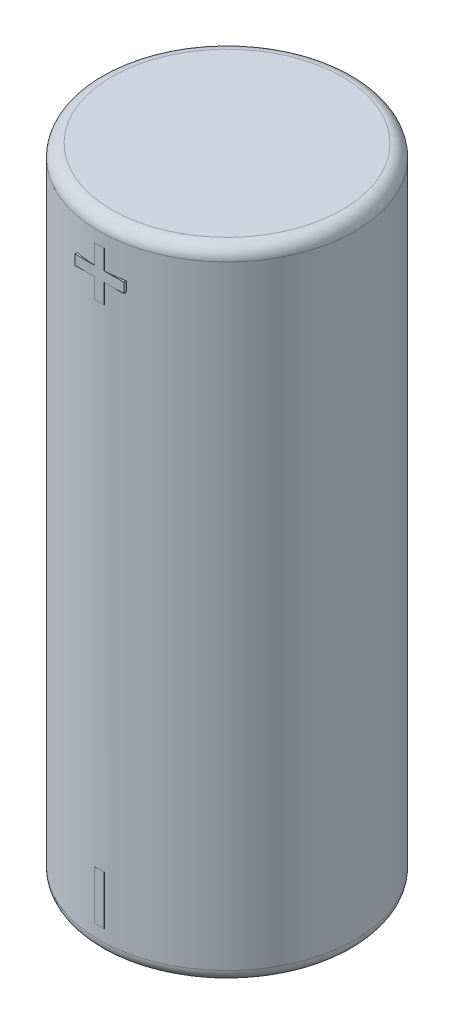
SolidWorks part; units mm, degrees
ref_plane "Front Plane" through (0, 0, 0) normal (0, 0, 1) x (1, 0, 0)
ref_plane "Top Plane" through (0, 0, 0) normal (0, 1, 0) x (1, 0, 0)
ref_plane "Right Plane" through (0, 0, 0) normal (1, 0, 0) x (0, 0, -1)
sketch "Sketch1" plane through (0, 0, 0) normal (0, 1, 0) x (1, 0, 0)
  circle A0 centre (0, 0) radius 13
  dimension "D1" = 26
extrude "Boss-Extrude1" add sketch "Sketch1" along normal blind 65
fillet "Fillet1" radius 1.27 1 edges at (0, 65, 13)
fillet "Fillet2" radius 1.27 1 edges at (0, 0, 13)
ref_plane "Plane1" through (0, 0, 13) normal (0, 0, 1) x (1, 0, 0)
sketch "Sketch2" plane through (0, 0, 13) normal (0, 0, 1) x (1, 0, 0)
  line L0 (11.73, 65) -> (-11.73, 65) construction
  line L1 (11.73, 65) -> (-11.73, 65)
  line L2 (0, 65) -> (0, 0) construction
  line L4 (-0.5, 62.5) -> (0.5, 62.5)
  line L5 (-0.5, 62.5) -> (-0.5, 57.5)
  line L6 (-0.5, 57.5) -> (0.5, 57.5)
  line L7 (0.5, 62.5) -> (0.5, 57.5)
  line L8 (-2.5, 60.5) -> (2.5, 60.5)
  line L9 (-2.5, 60.5) -> (-2.5, 59.5)
  line L10 (-2.5, 59.5) -> (2.5, 59.5)
  line L11 (2.5, 60.5) -> (2.5, 59.5)
  line L12 (-0.5, 7.5) -> (0.5, 7.5)
  line L13 (-0.5, 7.5) -> (-0.5, 2.5)
  line L14 (-0.5, 2.5) -> (0.5, 2.5)
  line L15 (0.5, 7.5) -> (0.5, 2.5)
  point P13 (0, 60)
  point P18 (0, 5)
  dimension "D1" = 5
  dimension "D2" = 5
  dimension "D3" = 1
  dimension "D4" = 1
  dimension "D5" = 0.5
  dimension "D6" = 2.5
  dimension "D7" = 5
  dimension "D8" = 0.5
  dimension "D9" = 2.5
  dimension "D10" = 1
  dimension "D11" = 5
  dimension "D12" = 5
  dimension "D13" = 2.5
  dimension "D14" = 0.5
extrude "Boss-Extrude2" add sketch "Sketch2" against normal blind 10 contours L2 L12 L13 L14 | L12 L2 L14 L15 | L5 L6 L7 L4 | L8 L11 L10 L9 region at (0.25, 5, 13) region at (-0.25, 5, 13)
sketch "Sketch3" plane through (0, 65, 0) normal (0, 1, 0) x (1, 0, 0)
  point P0 (0, 0)
sketch "Sketch4" plane through (0, 0, 0) normal (0, -1, 0) x (-1, 0, 0)
  point P0 (0, 0)
